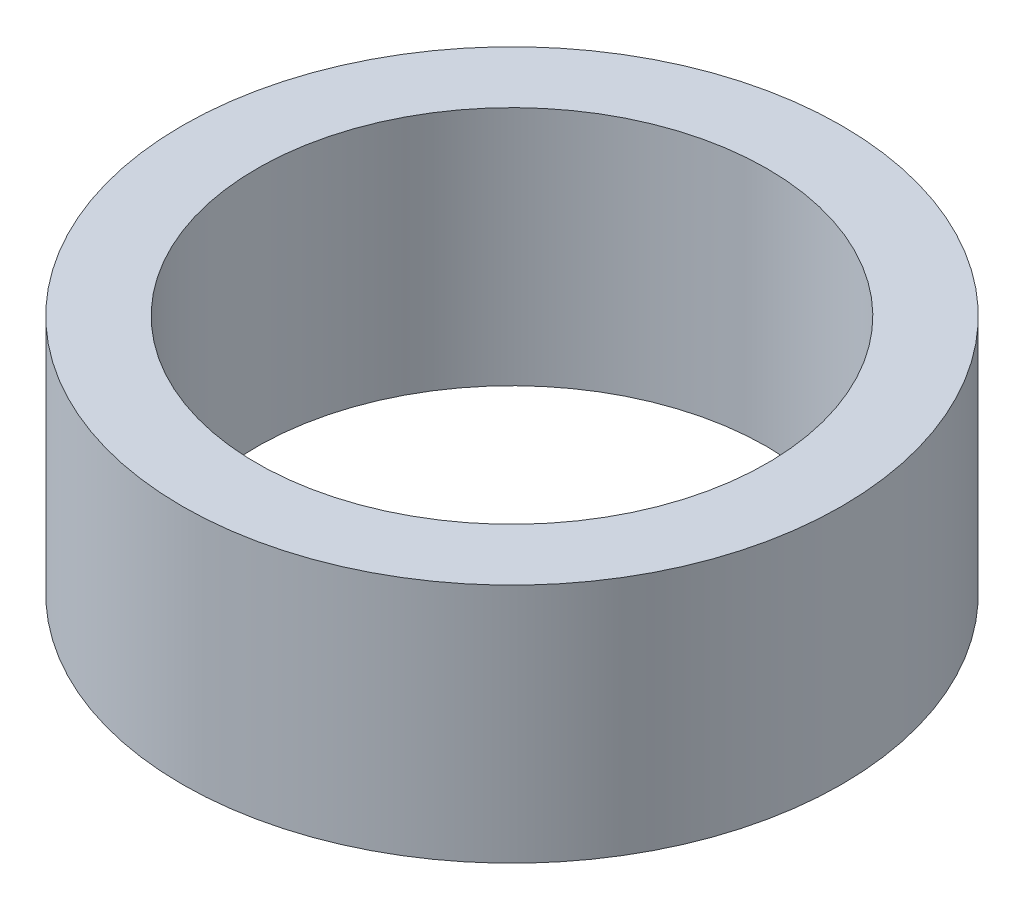
SolidWorks part; units mm, degrees
ref_plane "Front Plane" through (0, 0, 0) normal (0, 0, 1) x (1, 0, 0)
ref_plane "Top Plane" through (0, 0, 0) normal (0, 1, 0) x (1, 0, 0)
ref_plane "Right Plane" through (0, 0, 0) normal (1, 0, 0) x (0, 0, -1)
sketch "Sketch1" plane through (0, 0, 0) normal (0, 1, 0) x (1, 0, 0)
  circle A0 centre (0, 0) radius 44.5
  circle A1 centre (0, 0) radius 57.5
  dimension "D1" = 89
  dimension "D2" = 115
extrude "Boss-Extrude1" add sketch "Sketch1" along normal blind 42
